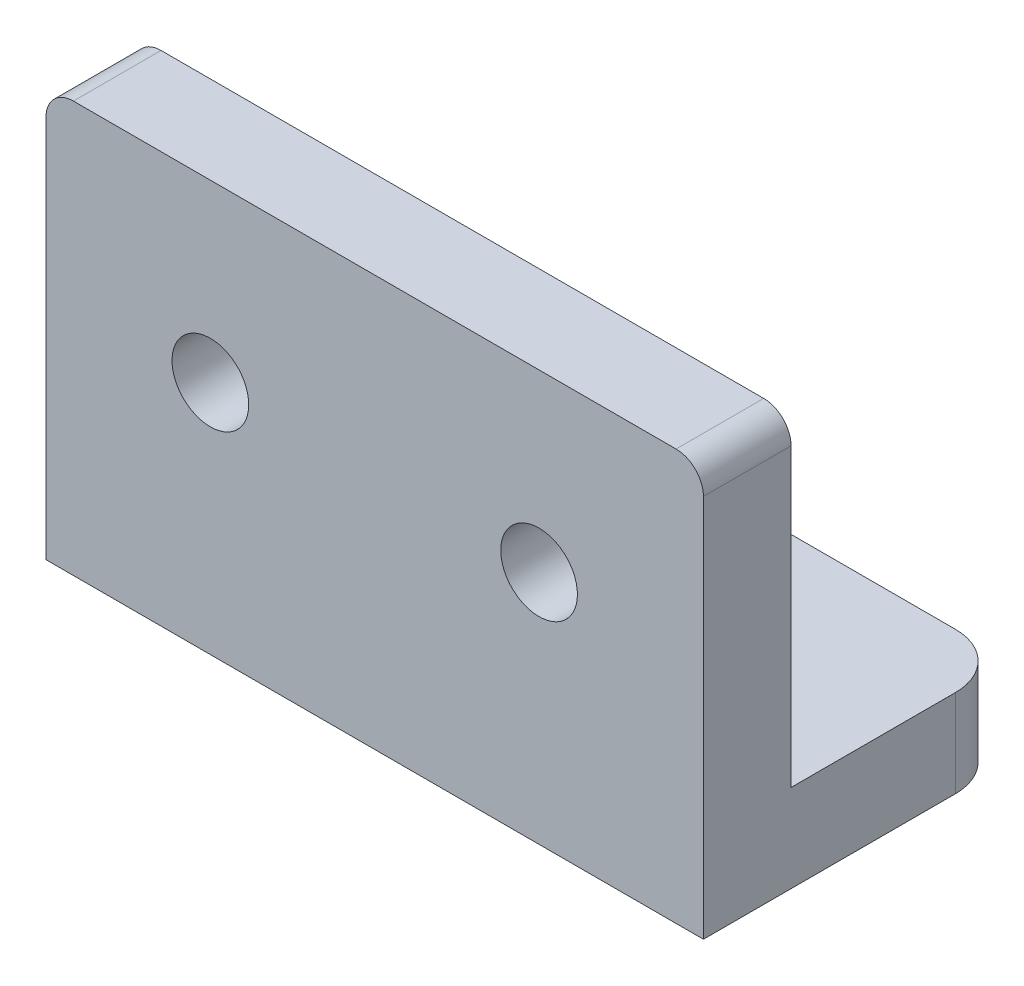
SolidWorks part; units mm, degrees
ref_plane "Front Plane" through (0, 0, 0) normal (0, 0, 1) x (1, 0, 0)
ref_plane "Top Plane" through (0, 0, 0) normal (0, 1, 0) x (1, 0, 0)
ref_plane "Right Plane" through (0, 0, 0) normal (1, 0, 0) x (0, 0, -1)
sketch "Sketch1" plane through (0, 0, 0) normal (0, 0, 1) x (1, 0, 0)
  line L1 (-15, 9.375) -> (15, 9.375)
  line L2 (-15, 9.375) -> (-15, -9.375)
  line L3 (-15, -9.375) -> (15, -9.375)
  line L4 (15, 9.375) -> (15, -9.375)
  line L5 (-15, 9.375) -> (15, -9.375) construction
  line L6 (-15, -9.375) -> (15, 9.375) construction
  point P0 (0, 0)
  dimension "D1" = 30
  dimension "D2" = 18.75
extrude "Boss-Extrude1" add sketch "Sketch1" along normal blind 4
fillet "Fillet1" radius 1.25 2 edges at (15, 9.375, 2) (-15, 9.375, 2)
sketch "Sketch3" plane through (0, 0, 4) normal (0, 0, 1) x (1, 0, 0)
  circle A0 centre (-7.5, 1.375) radius 1.75
  circle A1 centre (7.5, 1.375) radius 1.75
extrude "Cut-Extrude1" cut sketch "Sketch3" against normal blind 10
sketch "Sketch4" plane through (0, 0, 0) normal (0, 0, -1) x (-1, 0, 0)
  line L0 (15, 8.125) -> (15, -9.375) construction
  line L1 (-15, -9.375) -> (15, -9.375)
  line L2 (-15, -9.375) -> (-15, -5.375)
  line L3 (-15, -5.375) -> (15, -5.375)
  line L4 (15, -9.375) -> (15, -5.375)
  dimension "D1" = 4
extrude "Boss-Extrude2" add sketch "Sketch4" along normal blind 10
fillet "Fillet2" radius 2.5 2 edges at (15, -7.375, -10) (-15, -7.375, -10)
